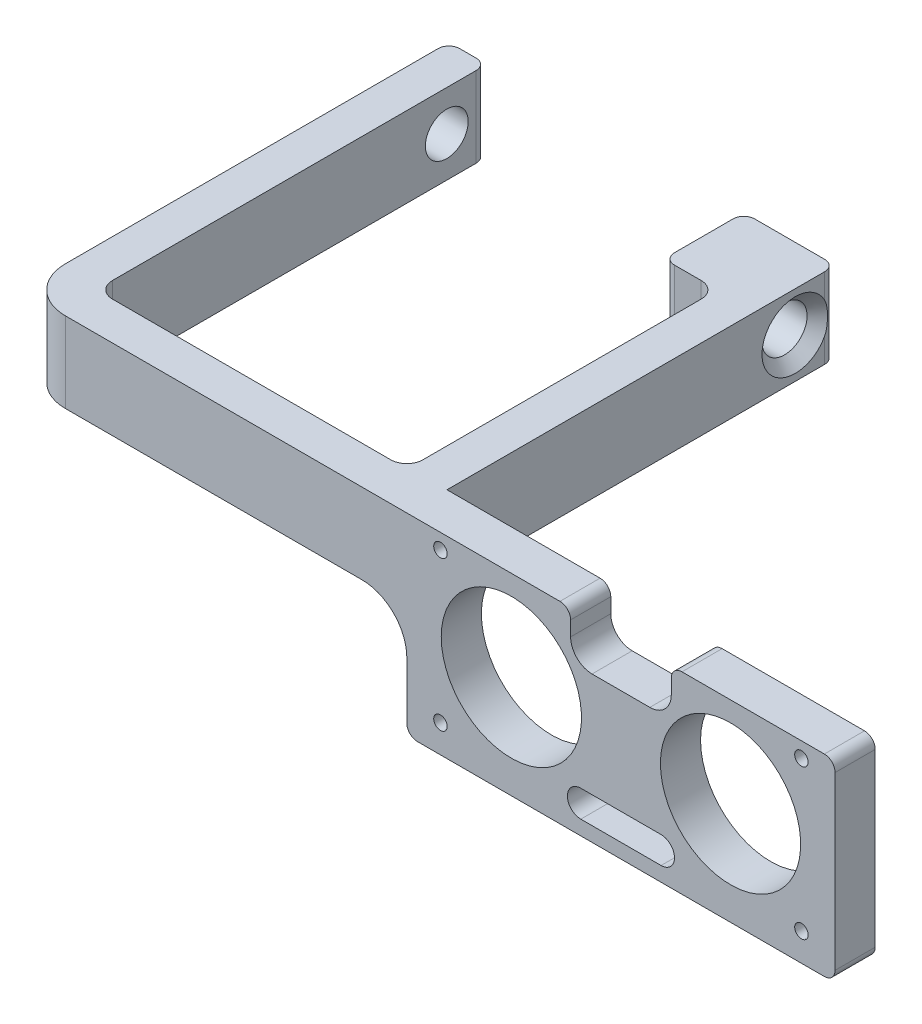
SolidWorks part; units mm, degrees
ref_plane "Front Plane" through (0, 0, 0) normal (0, 0, 1) x (1, 0, 0)
ref_plane "Top Plane" through (0, 0, 0) normal (0, 1, 0) x (1, 0, 0)
ref_plane "Right Plane" through (0, 0, 0) normal (1, 0, 0) x (0, 0, -1)
sketch "Sketch10" plane through (0, 0, 0) normal (0, 0, 1) x (1, 0, 0)
  line L0 (-21.41, 17.74) -> (-21.41, 0) construction
  line L1 (-21.41, 0) -> (21.41, 0) construction
  line L2 (21.41, 0) -> (21.41, 17.74) construction
  line L3 (21.41, 17.74) -> (-21.41, 17.74) construction
  line L4 (0, 0) -> (0, -3.312) construction
  line L5 (-13, 8.87) -> (13, 8.87) construction
  line L6 (13, 8.87) -> (21.41, 8.87) construction
  line L7 (0, 13.9911) -> (0, 0) construction
  line L8 (-4.7625, 0) -> (4.7625, 0) construction
  line L9 (-4.7625, 1.5875) -> (4.7625, 1.5875)
  line L10 (-4.7625, -1.5875) -> (4.7625, -1.5875)
  line L16 (5.969, 19.548) -> (5.969, 16.5311)
  line L17 (3.429, 13.9911) -> (-3.429, 13.9911)
  line L18 (-5.969, 16.5311) -> (-5.969, 19.548)
  line L19 (-5.969, 19.548) -> (-25.4, 19.548)
  line L20 (-25.4, 19.548) -> (-25.4, -3.312)
  line L21 (-25.4, -3.312) -> (25.4, -3.312)
  line L22 (25.4, -3.312) -> (25.4, 19.548)
  line L23 (25.4, 19.548) -> (5.969, 19.548)
  arc A0 (-4.7625, 1.5875) -> (-4.7625, -1.5875) centre (-4.7625, 0) ccw
  arc A1 (4.7625, -1.5875) -> (4.7625, 1.5875) centre (4.7625, 0) ccw
  arc A4 (3.429, 13.9911) -> (5.969, 16.5311) centre (3.429, 16.5311) ccw
  arc A5 (-5.969, 16.5311) -> (-3.429, 13.9911) centre (-3.429, 16.5311) ccw
  circle A8 centre (21.41, 17.74) radius 0.8
  circle A9 centre (21.41, 0) radius 0.8
  circle A10 centre (-21.41, 17.74) radius 0.8
  circle A11 centre (-21.41, 0) radius 0.8
  circle A12 centre (13, 8.87) radius 8.3185
  circle A13 centre (-13, 8.87) radius 8.3185
  point P31 (0, 0)
  dimension "D1" = 16.637
  dimension "D2" = 1.6
  dimension "D3" = 2.54
  dimension "D12" = 8.41
  dimension "D13" = 9.525
  dimension "D4" = 3.0169
  dimension "D5" = 6.858
  dimension "D6" = 1.808
  dimension "D7" = 17.74
  dimension "D8" = 42.82
  dimension "D9" = 50.8
  dimension "D10" = 22.86
  dimension "D11" = 26
  dimension "D14" = 3.175
extrude "Boss-Extrude1" add sketch "Sketch10" along normal blind 4.7625
sketch "Sketch11" plane through (0, 19.548, 0) normal (0, 1, 0) x (1, 0, 0)
  line L5 (-48.3235, -0.254) -> (-48.3235, -4.7625) construction
  line L10 (-25.4, -4.7625) -> (-25.4, 0) construction
  line L15 (0, -12.1603) -> (0, 51.5) construction
  line L16 (-29.9085, -0.254) -> (-25.4, -0.254) construction
  line L17 (-25.4, -4.7625) -> (-25.4, 46.0756)
  line L18 (-71.247, 46.0756) -> (-66.7385, 46.0756)
  line L19 (-71.247, -4.7625) -> (-71.247, 46.0756)
  line L20 (-25.4, -4.7625) -> (-71.247, -4.7625)
  line L21 (-25.4, 46.0756) -> (-36.2585, 46.0756)
  line L22 (-29.9085, 36.576) -> (-36.2585, 36.576)
  line L23 (-36.2585, 36.576) -> (-36.2585, 46.0756)
  line L24 (-29.9085, 36.576) -> (-29.9085, -0.254)
  line L25 (-66.7385, -0.254) -> (-29.9085, -0.254)
  line L26 (-66.7385, 46.0756) -> (-66.7385, -0.254)
  line L27 (-5.969, -4.7625) -> (-25.4, -4.7625) construction
  dimension "D1" = 36.83
  dimension "D2" = 9.4996
  dimension "D3" = 10.8585
  dimension "D4" = 6.35
  dimension "1.42" = 36.83
extrude "Boss-Extrude2" add sketch "Sketch11" against normal blind 9.525 contours L17 L21 L23 L22 L24 L25 L26 L18 L19 L20
fillet "Fillet1" radius 1.905 3 edges at (-29.9085, 14.7855, 0.254) (-66.7385, 14.7855, 0.254) (-29.9085, 14.7855, -36.576)
fillet "Fillet2" radius 5.334 2 edges at (-25.4, 10.023, 2.3813) (-71.247, 14.7855, 4.7625)
sketch "Sketch13" plane through (-25.4, 0, 0) normal (-1, 0, 0) x (0, 0, 1)
  line L0 (-41.3131, 14.7855) -> (-46.0756, 14.7855) construction
  line L2 (-41.3131, 14.7855) -> (-41.3131, 19.548) construction
  line L5 (-46.0756, 10.023) -> (-46.0756, 19.548) construction
  line L6 (0, 19.548) -> (-46.0756, 19.548) construction
  circle A0 centre (-41.3131, 14.7855) radius 2.675
  point P9 (-46.0756, 14.7855)
  dimension "D1" = 5.35
extrude "Cut-Extrude1" cut sketch "Sketch13" along normal up to next contours A0
sketch "Sketch14" plane through (-71.247, 0, 0) normal (-1, 0, 0) x (0, 0, 1)
  circle A0 centre (-41.3131, 14.7855) radius 2.54
  circle A2 centre (-41.3131, 14.7855) radius 2.675 construction
  dimension "D1" = 5.08
extrude "Cut-Extrude2" cut sketch "Sketch14" against normal through all
fillet "Fillet3" radius 1.27 11 edges at (-25.4, -3.312, 2.3813) (25.4, -3.312, 2.3813) (-5.969, 19.548, 2.3813) (5.969, 19.548, 2.3813) (-71.247, 14.7855, -46.0756) (-66.7385, 14.7855, -46.0756) (-36.2585, 14.7855, -36.576) (-36.2585, 14.7855, -46.0756) (-25.4, 14.7855, -46.0756) (25.4, 19.548, 2.3813) (-28.067, 10.023, 0)
chamfer "Chamfer1" distance 1.27 angle 45 1 edges at (-25.4, 12.1105, -41.3131)
